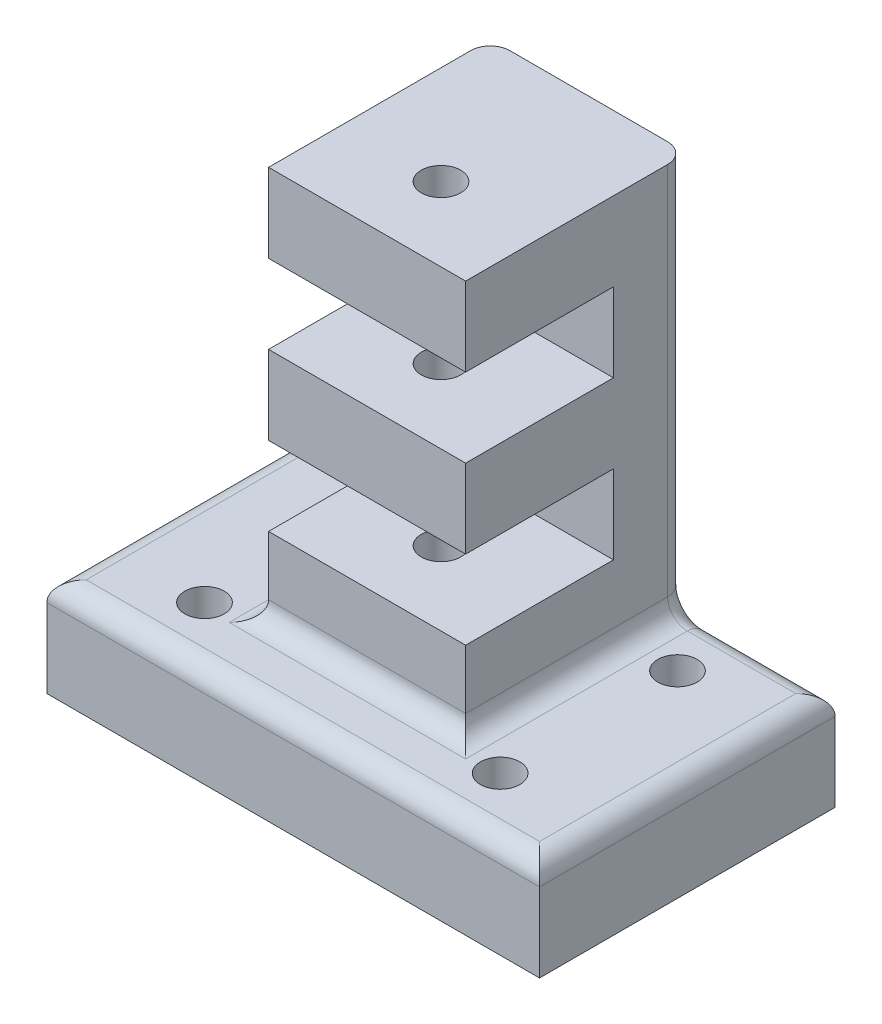
SolidWorks part; units mm, degrees
ref_plane "Front Plane" through (0, 0, 0) normal (0, 0, 1) x (1, 0, 0)
ref_plane "Top Plane" through (0, 0, 0) normal (0, 1, 0) x (1, 0, 0)
ref_plane "Right Plane" through (0, 0, 0) normal (1, 0, 0) x (0, 0, -1)
sketch "Sketch1" plane through (0, 0, 0) normal (0, 1, 0) x (1, 0, 0)
  line L1 (-25, 15) -> (25, 15)
  line L2 (-25, 15) -> (-25, -15)
  line L3 (-25, -15) -> (25, -15)
  line L4 (25, 15) -> (25, -15)
  line L5 (-25, 15) -> (25, -15) construction
  line L6 (-25, -15) -> (25, 15) construction
  line L7 (-15, 9) -> (15, 9)
  line L8 (-15, 9) -> (-15, -9) construction
  line L9 (-15, -9) -> (15, -9) construction
  line L10 (15, 9) -> (15, -9) construction
  circle A0 centre (-15, 9) radius 2
  circle A1 centre (15, 9) radius 2
  circle A2 centre (15, -9) radius 2
  circle A3 centre (-15, -9) radius 2
  dimension "D1" = 4
  dimension "D2" = 50
  dimension "D3" = 30
  dimension "D4" = 10
  dimension "D5" = 6
extrude "Boss-Extrude1" add sketch "Sketch1" against normal blind 10 contours L4 L1 L2 L3 A3 A2 A1 A0 region at (0, 0, 0)
sketch "Sketch2" plane through (0, 0, 0) normal (0, 1, 0) x (1, 0, 0)
  line L1 (-10, 15) -> (10, 15)
  line L2 (-10, 15) -> (-10, -15)
  line L3 (-10, -15) -> (10, -15)
  line L4 (10, 15) -> (10, -15)
  line L5 (-10, 15) -> (10, -15) construction
  line L6 (-10, -15) -> (10, 15) construction
  line L7 (-25, 15) -> (25, 15) construction
  point P0 (0, 0)
  point P8 (0, 0)
  dimension "D1" = 20
extrude "Boss-Extrude2" add sketch "Sketch2" along normal blind 40
sketch "Sketch3" plane through (10, 0, 0) normal (1, 0, 0) x (0, 0, -1)
  line L0 (0, 5.5) -> (0, -5.5) construction
  line L1 (-7.5, 32) -> (7.5, 32)
  line L2 (-7.5, 32) -> (-7.5, 24)
  line L3 (-7.5, 24) -> (7.5, 24)
  line L4 (7.5, 32) -> (7.5, 24)
  line L5 (-7.5, 32) -> (7.5, 24) construction
  line L6 (-7.5, 24) -> (7.5, 32) construction
  line L7 (-15, 40) -> (15, 40) construction
  line L8 (-7.5, 16) -> (7.5, 16)
  line L9 (-7.5, 16) -> (-7.5, 8)
  line L10 (-7.5, 8) -> (7.5, 8)
  line L11 (7.5, 16) -> (7.5, 8)
  line L12 (-7.5, 16) -> (7.5, 8) construction
  line L13 (-7.5, 8) -> (7.5, 16) construction
  point P0 (0, 28)
  point P7 (0, 12)
  dimension "D1" = 8
  dimension "D2" = 15
  dimension "D3" = 8
  dimension "D4" = 8
extrude "Cut-Extrude1" cut sketch "Sketch3" against normal up to next
sketch "Sketch4" plane through (0, 40, 0) normal (0, 1, 0) x (1, 0, 0)
  circle A0 centre (0, 0) radius 2
  dimension "D1" = 4
extrude "Cut-Extrude2" cut sketch "Sketch4" against normal through all and the other way through all contours A0
sketch "Sketch6" plane through (0, 0, 15) normal (0, 0, 1) x (1, 0, 0)
  line L0 (0, -5.5) -> (0, 5.5) construction
  line L1 (-10.0003, 50.6425) -> (10.0003, 50.6425)
  line L2 (-10.0003, 50.6425) -> (-10.0003, 0)
  line L3 (-10.0003, 0) -> (10.0003, 0)
  line L4 (10.0003, 50.6425) -> (10.0003, 0)
  line L5 (-10.0003, 50.6425) -> (10.0003, 0) construction
  line L6 (-10.0003, 0) -> (10.0003, 50.6425) construction
  line L7 (16.5, 0) -> (-16.5, 0) construction
  point P0 (0, 25.3212)
extrude "Cut-Extrude3" cut sketch "Sketch6" against normal up to surface (7.5 mm away) up to face at (0, 28, 7.5)
fillet "Fillet3" radius 2 3 edges at (-10, 0, -3.75) (0, 0, 7.5) (10, 0, -3.75)
fillet "Fillet4" radius 2 9 edges at (-10, 21, -15) (-10.5858, 0.5858, -15) (10, 21, -15) (10.5858, 0.5858, -15) (-18.5, 0, -15) (-25, 0, 0) (0, 0, 15) (25, 0, 0) (18.5, 0, -15)
